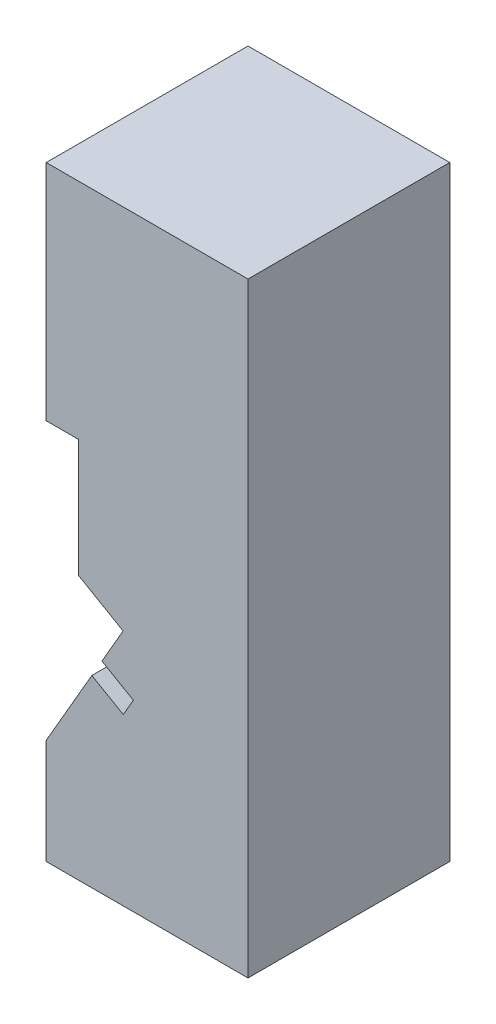
SolidWorks part; units mm, degrees
ref_plane "Front" through (0, 0, 0) normal (0, 0, 1) x (1, 0, 0)
ref_plane "Top" through (0, 0, 0) normal (0, 1, 0) x (1, 0, 0)
ref_plane "Right" through (0, 0, 0) normal (1, 0, 0) x (0, 0, -1)
sketch "Sketch1" plane through (0, 0, 0) normal (0, 1, 0) x (1, 0, 0)
  line L1 (-12.5, 12.5) -> (12.5, 12.5)
  line L2 (-12.5, 12.5) -> (-12.5, -12.5)
  line L3 (-12.5, -12.5) -> (12.5, -12.5)
  line L4 (12.5, 12.5) -> (12.5, -12.5)
  line L5 (-12.5, 12.5) -> (12.5, -12.5) construction
  line L6 (-12.5, -12.5) -> (12.5, 12.5) construction
  point P0 (0, 0)
  dimension "D1" = 25
  dimension "D2" = 25
extrude "Boss-Extrude2" add sketch "Sketch1" along normal mid plane 75 contours L1 L4 L3 L2
sketch "Sketch2" plane through (0, 0, 12.5) normal (0, 0, 1) x (1, 0, 0)
  line L0 (-12.5, 37.5) -> (-12.5, -37.5) construction
  line L1 (-12.5, 6.5) -> (12.5, 6.5)
  line L2 (-12.5, 6.5) -> (-12.5, -17.5)
  line L3 (-12.5, -17.5) -> (12.5, -17.5)
  line L4 (12.5, 6.5) -> (12.5, -17.5)
  line L5 (12.5, 37.5) -> (12.5, -37.5) construction
  line L6 (-12.5, -37.5) -> (12.5, -37.5) construction
  dimension "D1" = 20
  dimension "D2" = 24
extrude "Cut-Extrude1" [suppressed] cut sketch "Sketch2" against normal blind 12.5
sketch "Sketch3" [suppressed] plane through (0, 0, 0) normal (0, 0, 1) x (1, 0, 0)
  line L0 (-3.75, 6.5) -> (-3.75, 1.25)
  line L1 (12.5, 6.5) -> (-12.5, 6.5) construction
  line L2 (-3.75, 1.25) -> (0.75, 1.25)
  line L3 (0.75, 1.25) -> (0.75, -1.25)
  line L4 (0.75, -1.25) -> (-3.75, -1.25)
  line L5 (-3.75, -1.25) -> (-3.75, -17.5)
  line L6 (-12.5, -17.5) -> (12.5, -17.5) construction
  line L7 (-3.75, -17.5) -> (12.5, -17.5)
  line L8 (12.5, -17.5) -> (12.5, 6.5)
  line L9 (12.5, 6.5) -> (-3.75, 6.5)
  dimension "D1" = 5.25
  dimension "D2" = 2.5
  dimension "D3" = 16.25
  dimension "D4" = 4.5
extrude "Boss-Extrude3" [suppressed] add sketch "Sketch3" along normal blind 12.5
sketch "Sketch5" plane through (0, 0, 12.5) normal (0, 0, 1) x (1, 0, 0)
  line L0 (-8.5, -4.8094) -> (-2.9737, -8)
  line L1 (-12.5, 37.5) -> (-12.5, -37.5) construction
  line L2 (-2.9737, -8) -> (-5.5987, -12.5466)
  line L3 (-5.5987, -12.5466) -> (-1.7016, -14.7966)
  line L4 (-1.7016, -14.7966) -> (-2.9516, -16.9617)
  line L5 (-2.9516, -16.9617) -> (-6.8487, -14.7117)
  line L6 (-6.8487, -14.7117) -> (-12.5, -24.5)
  line L7 (-12.5, 9.7906) -> (-12.5, -24.5)
  line L8 (-12.5, -37.5) -> (12.5, -37.5) construction
  line L9 (-12.5, 9.7906) -> (-8.5, 9.7906)
  line L10 (-8.5, 9.7906) -> (-8.5, -4.8094)
  point P13 (-12.5, 12.487)
  dimension "D1" = 5.25
  dimension "D2" = 30
  dimension "D3" = 4.5
  dimension "D4" = 2.5
  dimension "D5" = 34.2906
  dimension "D6" = 13
  dimension "D7" = 4
  dimension "D8" = 14.6
extrude "Cut-Extrude2" cut sketch "Sketch5" against normal blind 12.5
